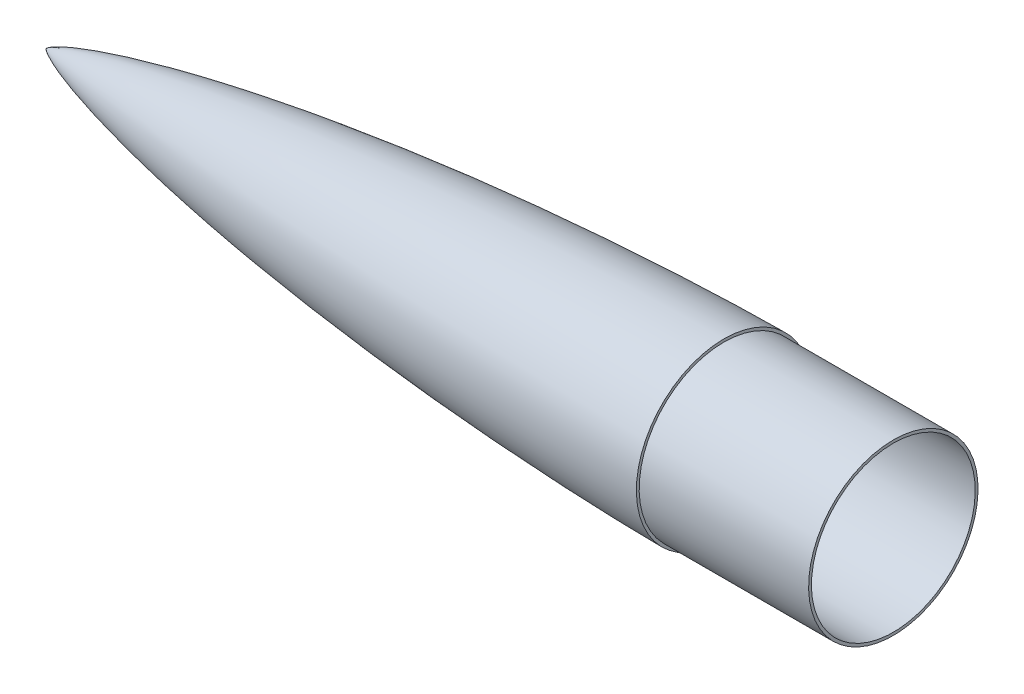
SolidWorks part; units mm, degrees
material "Hexcel AS4C (3000 Filaments)"
ref_plane "Plan de face"
ref_plane "Plan de dessus" through (0, 0, 0) normal (0, 1, 0) x (1, 0, 0)
ref_plane "Plan de droite" through (0, 0, 0) normal (1, 0, 0) x (0, 0, -1)
sketch "Esquisse1" plane through (0, 0, 0) normal (0, 0, 1) x (1, 0, 0)
  line L0 (2700, 0) -> (2700, 77.47) construction
  line L1 (2700, 77.47) -> (600, 77.47) construction
  line L2 (2700, 0) -> (0, 0) construction
  line L3 (600, 77.47) -> (600, 0)
  line L4 (1650, 77.47) -> (1650, 0) construction
  line L5 (600, 77.47) -> (600, 0) construction
  line L8 (0, 0) -> (600, 0)
  spline S0 degree 4 poles (0, 0) (0.0014, 0.0067) (0.0048, 0.0199) (0.0149, 0.0453) (0.0401, 0.0938) (0.0807, 0.157) (0.1383, 0.2334) (0.2203, 0.33) (0.3192, 0.4351) (0.4349, 0.5479) (0.5674, 0.6679) (0.7714, 0.8421) (1.1052, 1.1052) (1.6952, 1.526) (2.7478, 2.1929) (4.5887, 3.222) (7.8542, 4.817) (13.5227, 7.2186) (23.0835, 10.7182) (38.7362, 15.6536) (62.1009, 21.9639) (92.1582, 28.9163) (127.2376, 35.933) (164.7304, 42.4831) (202.346, 48.2813) (240.0557, 53.429) (277.8398, 57.9952) (315.6844, 62.0289) (353.5783, 65.5666) (391.513, 68.6356) (429.4812, 71.2564) (467.4769, 73.4429) (500.7425, 74.9827) (529.2668, 76.0339) (552.967, 76.7206) (569.499, 77.0956) (583.6166, 77.3332) (592.9784, 77.4344) (597.6594, 77.4658) (600, 77.47) knots 0 0 0 0 0 0.000045 0.00009 0.00018 0.000359 0.000539 0.000718 0.001013 0.001308 0.001601 0.001895 0.002778 0.004104 0.006368 0.010089 0.016647 0.028004 0.046856 0.077052 0.124599 0.187199 0.249799 0.312399 0.374999 0.4376 0.5002 0.5628 0.6254 0.688 0.7506 0.813201 0.875801 0.907101 0.938401 0.9692 0.9846 1 1 1 1 1 construction
  spline S1 degree 4 poles (0, 0) (0.0014, 0.0067) (0.0048, 0.0199) (0.0149, 0.0453) (0.0401, 0.0938) (0.0807, 0.157) (0.1383, 0.2334) (0.2203, 0.33) (0.3192, 0.4351) (0.4349, 0.5479) (0.5674, 0.6679) (0.7714, 0.8421) (1.1052, 1.1052) (1.6952, 1.526) (2.7478, 2.1929) (4.5887, 3.222) (7.8542, 4.817) (13.5227, 7.2186) (23.0835, 10.7182) (38.7362, 15.6536) (62.1009, 21.9639) (92.1582, 28.9163) (127.2376, 35.933) (164.7304, 42.4831) (202.346, 48.2813) (240.0557, 53.429) (277.8398, 57.9952) (315.6844, 62.0289) (353.5783, 65.5666) (391.513, 68.6356) (429.4812, 71.2564) (467.4769, 73.4429) (500.7425, 74.9827) (529.2668, 76.0339) (552.967, 76.7206) (569.499, 77.0956) (583.6166, 77.3332) (592.9784, 77.4344) (597.6594, 77.4658) (600, 77.47) knots 0 0 0 0 0 0.000045 0.00009 0.00018 0.000359 0.000539 0.000718 0.001013 0.001308 0.001601 0.001895 0.002778 0.004104 0.006368 0.010089 0.016647 0.028004 0.046856 0.077052 0.124599 0.187199 0.249799 0.312399 0.374999 0.4376 0.5002 0.5628 0.6254 0.688 0.7506 0.813201 0.875801 0.907101 0.938401 0.9692 0.9846 1 1 1 1 1
  dimension "Ltot" = 2700
  dimension "R" = 77.47
  dimension "Ln" = 600
revolve "Révolution2" add sketch "Esquisse1" angle 360 about L2
sketch "Esquisse2" plane through (600, 0, 0) normal (1, 0, 0) x (0, 0, -1)
  circle A0 centre (0, 0) radius 75
  circle A1 centre (0, 0) radius 72.5
  dimension "D1" = 150
  dimension "D2" = 145
extrude "Boss.-Extru.1" add sketch "Esquisse2" along normal blind 150
